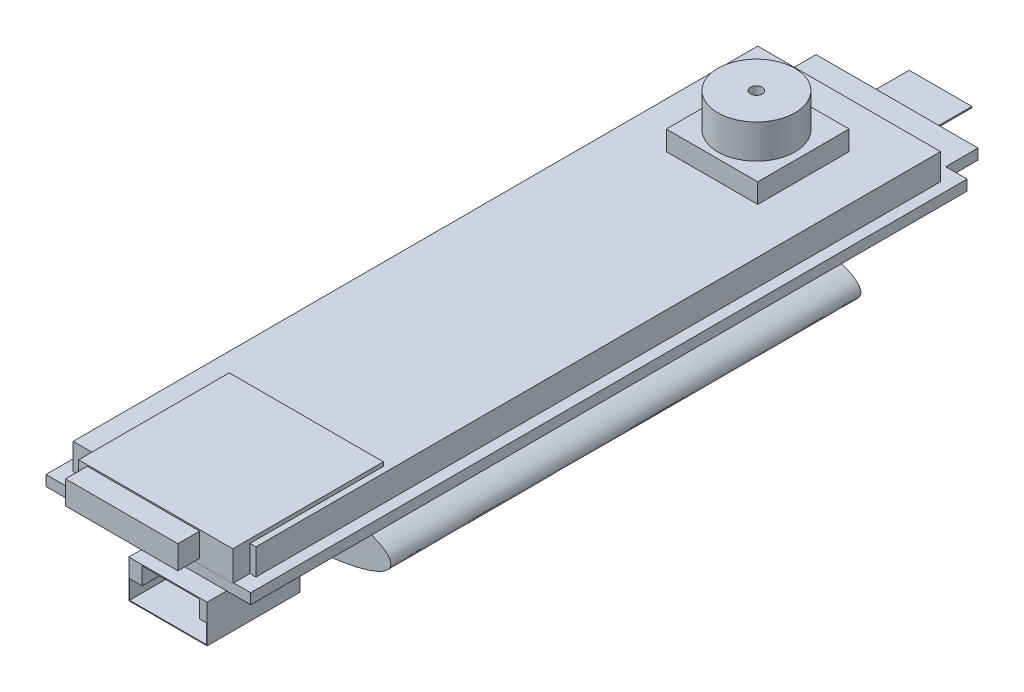
SolidWorks part; units mm, degrees
ref_plane "Front Plane" through (0, 0, 0) normal (0, 0, 1) x (1, 0, 0)
ref_plane "Top Plane" through (0, 0, 0) normal (0, 1, 0) x (1, 0, 0)
ref_plane "Right Plane" through (0, 0, 0) normal (1, 0, 0) x (0, 0, -1)
sketch "Sketch4" plane through (0, 0, 0) normal (0, 0, 1) x (1, 0, 0)
  line L1 (-6.35, -0.508) -> (6.35, -0.508)
  line L2 (-6.35, -0.508) -> (-6.35, -1.905)
  line L3 (-6.35, -1.905) -> (6.35, -1.905)
  line L4 (6.35, -0.508) -> (6.35, -1.905)
extrude "Boss-Extrude2" add sketch "Sketch4" along normal blind 6.35 and the other way blind 6.35 from offset 15.24
sketch "Sketch5" plane through (0, 0, 0) normal (0, 0, 1) x (1, 0, 0)
  ellipse E0 centre (0, -3.81) end of major axis (10.033, -3.81) minor radius 2.5896
extrude "Boss-Extrude3" add sketch "Sketch5" along normal blind 22.86 and the other way blind 22.86
sketch "Sketch6" plane through (0, 0, 0) normal (0, 0, 1) x (1, 0, 0)
  line L1 (-9.9568, 0.508) -> (9.9568, 0.508)
  line L2 (-9.9568, 0.508) -> (-9.9568, -0.508)
  line L3 (-9.9568, -0.508) -> (9.9568, -0.508)
  line L4 (9.9568, 0.508) -> (9.9568, -0.508)
  line L5 (-9.9568, 0.508) -> (9.9568, -0.508) construction
  line L6 (-9.9568, -0.508) -> (9.9568, 0.508) construction
  point P0 (0, 0)
extrude "Boss-Extrude4" add sketch "Sketch6" along normal blind 36.4109 and the other way blind 36.4109
sketch "Sketch7" plane through (0, 0.508, 0) normal (0, 1, 0) x (1, 0, 0)
  line L1 (8.3058, -36.5057) -> (-6.6869, -36.5057)
  line L2 (8.3058, -36.5057) -> (8.3058, -21.8567)
  line L3 (8.3058, -21.8567) -> (-6.6869, -21.8567)
  line L4 (-6.6869, -36.5057) -> (-6.6869, -21.8567)
extrude "Boss-Extrude6" add sketch "Sketch7" along normal blind 2.921
sketch "Sketch10" plane through (0, 0, 36.5057) normal (0, 0, 1) x (1, 0, 0)
  line L1 (-5.842, 1.016) -> (5.08, 1.016)
  line L2 (-5.842, 1.016) -> (-5.842, 3.302)
  line L3 (-5.842, 3.302) -> (5.08, 3.302)
  line L4 (5.08, 1.016) -> (5.08, 3.302)
extrude "Boss-Extrude7" add sketch "Sketch10" along normal offset from surface (2.115 mm away) 75.0316 up to face at (0, 0, -36.4109)
sketch "Sketch11" plane through (0, 0.508, 0) normal (0, 1, 0) x (1, 0, 0)
  line L1 (-9.9568, 36.4109) -> (-7.874, 36.4109)
  line L2 (-9.9568, 36.4109) -> (-9.9568, 33.274)
  line L3 (-9.9568, 33.274) -> (-7.874, 33.274)
  line L4 (-7.874, 36.4109) -> (-7.874, 33.274)
  line L5 (9.9568, 36.4109) -> (7.874, 36.4109)
  line L6 (9.9568, 36.4109) -> (9.9568, 33.274)
  line L7 (9.9568, 33.274) -> (7.874, 33.274)
  line L8 (7.874, 36.4109) -> (7.874, 33.274)
extrude "Cut-Extrude1" cut sketch "Sketch11" against normal up to next
sketch "Sketch12" plane through (0, -0.508, 0) normal (0, -1, 0) x (1, 0, 0)
  line L1 (0, 29.2989) -> (7.62, 29.2989)
  line L2 (0, 29.2989) -> (0, 38.3159)
  line L3 (0, 38.3159) -> (7.62, 38.3159)
  line L4 (7.62, 29.2989) -> (7.62, 38.3159)
extrude "Boss-Extrude8" add sketch "Sketch12" along normal blind 3.683
sketch "Sketch13" plane through (0, 0.508, 0) normal (0, 1, 0) x (1, 0, 0)
  line L1 (-4.445, 27.305) -> (4.445, 27.305)
  line L2 (-4.445, 27.305) -> (-4.445, 18.415)
  line L3 (-4.445, 18.415) -> (4.445, 18.415)
  line L4 (4.445, 27.305) -> (4.445, 18.415)
extrude "Boss-Extrude9" add sketch "Sketch13" along normal blind 4.445
sketch "Sketch14" plane through (0, 4.953, 0) normal (0, 1, 0) x (1, 0, 0)
  line L0 (0, -5.4057) -> (0, 5.4057) construction
  circle A0 centre (0, 22.733) radius 3.7485
extrude "Boss-Extrude10" add sketch "Sketch14" along normal blind 3.302
sketch "Sketch15" plane through (0, 8.255, 0) normal (0, 1, 0) x (1, 0, 0)
  circle A2 centre (0, 22.733) radius 0.5735
  circle A3 centre (0, 22.733) radius 0.5735
  dimension "D1" = 3.175
extrude "Cut-Extrude2" cut sketch "Sketch15" against normal blind 3.302
sketch "Sketch16" plane through (0, -0.508, 0) normal (0, -1, 0) x (1, 0, 0)
  line L0 (-7.874, -36.4109) -> (7.874, -36.4109) construction
  line L1 (-7.112, -36.4109) -> (7.112, -36.4109)
  line L2 (-7.112, -36.4109) -> (-7.112, -30.48)
  line L3 (-7.112, -30.48) -> (7.112, -30.48)
  line L4 (7.112, -36.4109) -> (7.112, -30.48)
  line L6 (-3.048, -36.4109) -> (3.048, -36.4109)
  line L7 (-3.048, -36.4109) -> (-3.048, -40.64)
  line L8 (-3.048, -40.64) -> (3.048, -40.64)
  line L9 (3.048, -36.4109) -> (3.048, -40.64)
extrude "Boss-Extrude11" add sketch "Sketch16" along normal blind 0.127 contours L9 L1 L7 L8 | L1 L4 L3 L2 region at (0, -0.508, -38.5254)
sketch "Sketch17" plane through (0, 0, 38.3159) normal (0, 0, 1) x (1, 0, 0)
  line L4 (1.3053, -0.6096) -> (6.8892, -0.6096)
  line L7 (0.0762, -2.2878) -> (1.3053, -2.2878)
  line L8 (1.3053, -0.6096) -> (1.3053, -2.2878)
  line L11 (7.5438, -2.2878) -> (6.8892, -2.2878)
  line L16 (6.8892, -0.6096) -> (6.8892, -2.2878)
  line L17 (0.0762, -2.2878) -> (0.0762, -4.1148)
  line L18 (0.0762, -4.1148) -> (7.5438, -4.1148)
  line L19 (7.5438, -2.2878) -> (7.5438, -4.1148)
extrude "Cut-Extrude3" cut sketch "Sketch17" against normal blind 6.35
sketch "Sketch18" plane through (0, 0.508, 0) normal (0, 1, 0) x (1, 0, 0)
  line L0 (8.3058, -36.5057) -> (8.3058, -21.8567) construction
  line L1 (8.89, -34.8382) -> (-8.89, -34.8382)
  line L2 (8.89, -34.8382) -> (8.89, 31.75)
  line L3 (8.89, 31.75) -> (-8.89, 31.75)
  line L4 (-8.89, -34.8382) -> (-8.89, 31.75)
  line L5 (-4.445, 27.305) -> (4.445, 27.305)
  line L6 (-4.445, 27.305) -> (-4.445, 18.415)
  line L7 (-4.445, 18.415) -> (4.445, 18.415)
  line L8 (4.445, 27.305) -> (4.445, 18.415)
  line L9 (-6.6869, -21.8567) -> (8.3058, -21.8567)
  line L10 (-6.6869, -21.8567) -> (-6.6869, -34.8382)
  line L11 (-6.6869, -34.8382) -> (8.3058, -34.8382)
  line L12 (8.3058, -21.8567) -> (8.3058, -34.8382)
  line M1 (-6.6869, -21.8567) -> (8.3058, -21.8567)
  line M2 (8.3058, -21.8567) -> (8.3058, -36.4109)
  line M4 (-6.6869, -36.4109) -> (-6.6869, -21.8567)
  line M13 (4.445, 18.415) -> (-4.445, 18.415)
  line M14 (-4.445, 18.415) -> (-4.445, 27.305)
  line M15 (-4.445, 27.305) -> (4.445, 27.305)
  line M16 (4.445, 27.305) -> (4.445, 18.415)
extrude "Boss-Extrude13" add sketch "Sketch18" along normal blind 2.54 contours L4 L1 L2 L3 M4 M1 M2 M16 M13 M14 M15 region at (-0.1731, 0.508, -2.0679)
